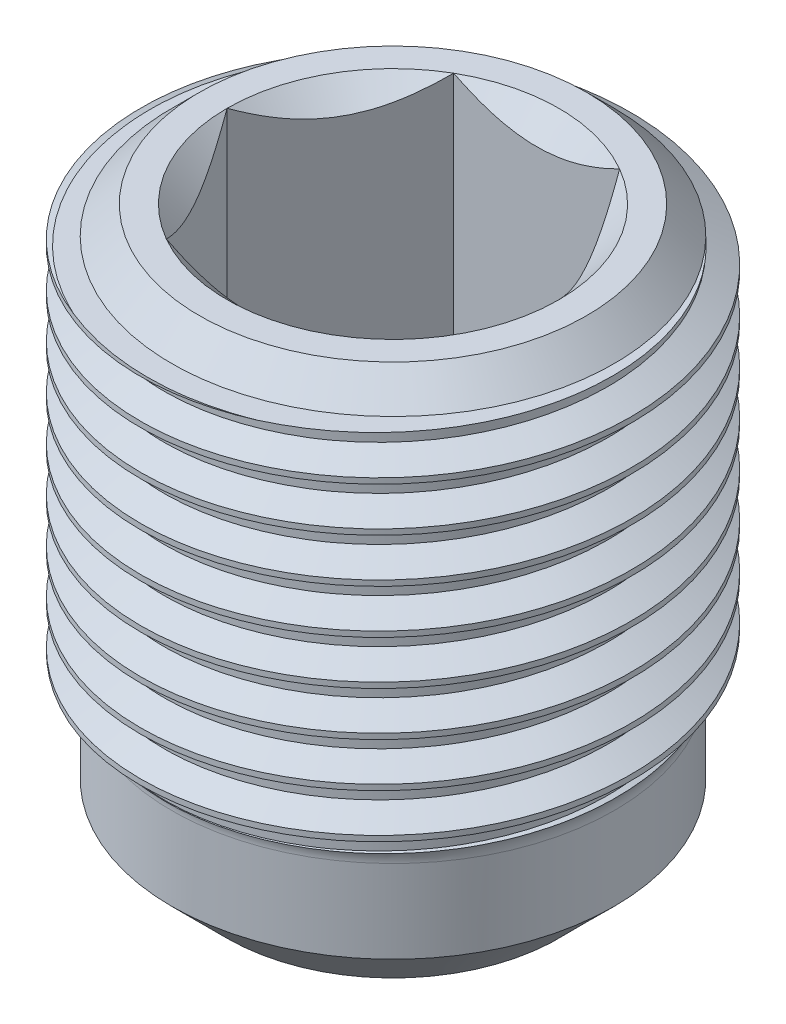
SolidWorks part; units mm, degrees
ref_plane "前视基准面" through (0, 0, 0) normal (0, 0, 1) x (1, 0, 0)
ref_plane "上视基准面" through (0, 0, 0) normal (0, 1, 0) x (1, 0, 0)
ref_plane "右视基准面" through (0, 0, 0) normal (1, 0, 0) x (0, 0, -1)
sketch "Sketch1" plane through (0, 0, 0) normal (0, 0, 1) x (1, 0, 0)
  line L0 (0, 3.5) -> (-1.5, 5)
  line L1 (0, 0) -> (-2, 0)
  line L2 (0, 0) -> (0, 3.5)
  line L3 (-1.5, 5) -> (-2, 5)
  line L4 (-2, 0) -> (-2, 5)
  point P2 (0, 5)
  dimension "D1" = 5
  dimension "D2" = 2
revolve "Revolve1" add sketch "Sketch1" angle 360 about L2
thread "Thread1" pitch 0.4 method extrude profile "Sketch3" start angle 0, offset 1, length 5, pitch 0.4, diameter 4
ref_plane "Plane1" through (-2, 6, 0) normal (0, 0, 1) x (-1, 0, 0)
sketch "Sketch3" plane through (-2, 6, 0) normal (0, 0, 1) x (-1, 0, 0)
  line L0 (0, 0) -> (0, 0.4) construction
  line L1 (0, 0) -> (0.2165, 0.125)
  line L2 (0.2165, 0.125) -> (0.2165, 0.175)
  line L3 (0.2165, 0.175) -> (0, 0.3)
  line L4 (0.2165, 0.15) -> (0, 0.15) construction
  line L11 (0, 0) -> (0, 0.3)
  point P2 (0, 0)
  dimension "Pitch" = 0.4
  dimension "Profile_Angle" = 60
  dimension "Profile_Land" = 0.05
  dimension "Profile_Height" = 0.2165
sketch "Sketch6" plane through (0, 0, 0) normal (0, 0, 1) x (1, 0, 0)
  line L0 (-1.5, 5) -> (-2, 5) construction
  line L1 (-1.75, 5) -> (-2, 4.75)
  line L2 (-2, 0) -> (-2, 5) construction
  line L3 (-2, 5) -> (0, 5)
  line L4 (0, 5) -> (0, 6.75)
  line L5 (0, 6.75) -> (-2.5, 6.75)
  line L6 (-2.5, 6.75) -> (-2.5, 4.75)
  line L7 (-2.5, 4.75) -> (-2, 4.75)
  line L8 (-1.5, 0) -> (-2, 0.5)
  line L9 (0, 0) -> (-2, 0) construction
  line L10 (-2, 0.5) -> (-2, 1.25)
  line L11 (-2.25, 1.5) -> (-2.5, 1.5)
  line L12 (-2.5, 1.5) -> (-2.5, -1)
  line L13 (-2.5, -1) -> (-1.5, -1)
  line L14 (-1.5, -1) -> (-1.5, 0)
  arc A0 (-2, 1.25) -> (-2.25, 1.5) centre (-2.25, 1.25) ccw
  point P25 (-2, 1.5)
  dimension "D8" = 0.25
  dimension "D1" = 45
  dimension "D2" = 2
  dimension "D3" = 2.5
  dimension "D4" = 0.5
  dimension "D5" = 45
  dimension "D6" = 2.5
  dimension "D7" = 1.5
revolve "Cut-Revolve2" cut sketch "Sketch6" angle 360 about L2 region at (-1.2822, 5.8408, 0) region at (-2.0891, 0.0344, 0)
sketch "Sketch7" plane through (0, 5, 0) normal (0, 1, 0) x (1, 0, 0)
  line L1 (0.75, 1.299) -> (-0.75, 1.299)
  line L2 (-0.75, 1.299) -> (-1.5, 0)
  line L3 (-1.5, 0) -> (-0.75, -1.299)
  line L4 (-0.75, -1.299) -> (0.75, -1.299)
  line L5 (0.75, -1.299) -> (1.5, 0)
  line L6 (1.5, 0) -> (0.75, 1.299)
  circle A0 centre (0, 0) radius 1.299 construction
extrude "Cut-Extrude1" cut sketch "Sketch7" against normal blind 2.5
fillet "Fillet1" radius 0.05 6 edges at (1.125, 2.5, 0.6495) (0, 2.5, 1.299) (-1.125, 2.5, 0.6495) (-1.125, 2.5, -0.6495) (0, 2.5, -1.299) (1.125, 2.5, -0.6495)
